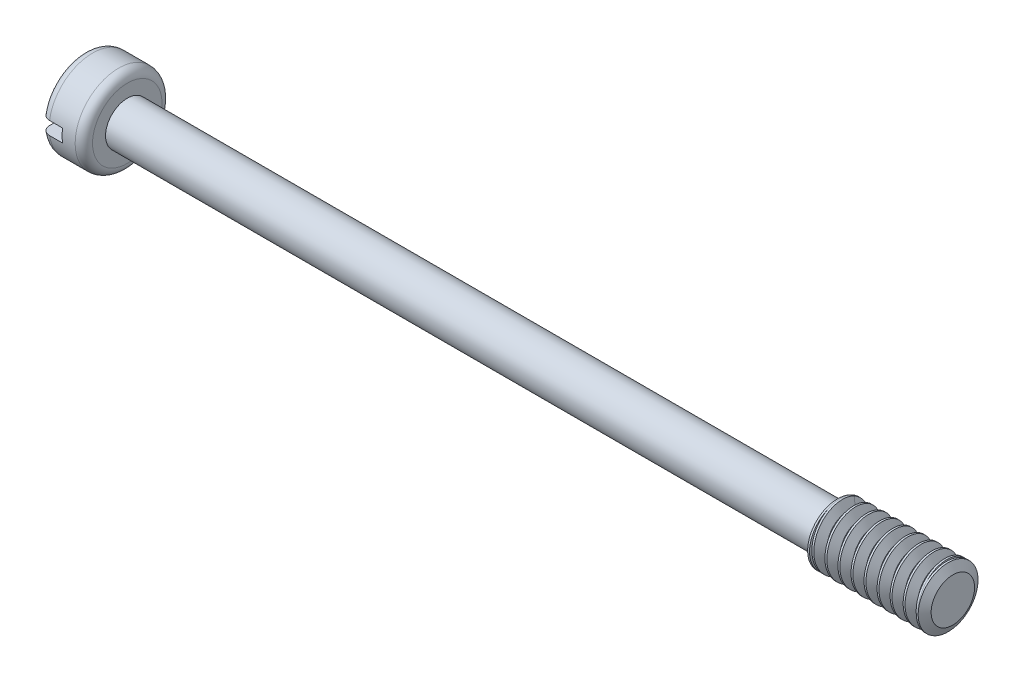
SolidWorks part; units mm, degrees
ref_plane "前视基准面" through (0, 0, 0) normal (0, 0, 1) x (1, 0, 0)
ref_plane "上视基准面" through (0, 0, 0) normal (0, 1, 0) x (1, 0, 0)
ref_plane "右视基准面" through (0, 0, 0) normal (1, 0, 0) x (0, 0, -1)
sketch "草图1" plane through (0, 0, 0) normal (0, 0, 1) x (1, 0, 0)
  line L0 (0, 0) -> (20, 0)
  line L1 (20, 0) -> (20, 0.5)
  line L2 (20, 0.5) -> (1, 0.5)
  line L3 (1, 0.5) -> (1, 0.8)
  line L4 (0.8, 1) -> (0.2, 1)
  line L5 (0, 0.8) -> (0, 0)
  arc A0 (0.2, 1) -> (0, 0.8) centre (0.2, 0.8) ccw
  arc A1 (1, 0.8) -> (0.8, 1) centre (0.8, 0.8) ccw
  point P9 (0, 1)
  point P12 (1, 1)
  dimension "D5" = 0.2
  dimension "D1" = 1
  dimension "D2" = 20
  dimension "D3" = 0.5
  dimension "D4" = 1
revolve "旋转1" add sketch "草图1" angle 360 about L0
thread "螺纹线1" pitch 0.35 method extrude profile "螺纹线轮廓1" start angle 0, offset 0, length 2.5, pitch 0.3, diameter 1
ref_plane "基准面4" through (20, 0, 0.5) normal (0, -1, 0) x (0, 0, 1)
sketch "螺纹线轮廓1" plane through (20, 0, 0.5) normal (0, -1, 0) x (0, 0, 1)
  line L0 (0, 0) -> (0, 0.35) construction
  line L1 (0, 0) -> (0.1894, 0.1094)
  line L2 (0.1894, 0.1094) -> (0.1894, 0.1531)
  line L3 (0.1894, 0.1531) -> (0, 0.2625)
  line L4 (0.1894, 0.1312) -> (0, 0.1312) construction
  line L11 (0, 0) -> (0, 0.2625)
  point P2 (0, 0)
  dimension "Pitch" = 0.35
  dimension "Profile_Angle" = 60
  dimension "Profile_Land" = 0.0437
  dimension "Profile_Height" = 0.1894
sketch "草图5" plane through (0, 0, 0) normal (0, -1, 0) x (1, 0, 0)
  line L0 (0, 0) -> (20.9351, 0) construction
  line L4 (19.8906, 0.6894) -> (19.8469, 0.6894)
  line L5 (19.8469, 0.6894) -> (19.7375, 0.5)
  line L6 (19.7375, 0.5) -> (20, 0.5)
  line L7 (20, 0.5) -> (19.8906, 0.6894)
  line L8 (19.8906, 0.6894) -> (19.8469, 0.6894)
  line L9 (19.8469, 0.6894) -> (19.7375, 0.5)
  line L10 (19.7375, 0.5) -> (20, 0.5)
  line L11 (20, 0.5) -> (19.8906, 0.6894)
  dimension "D1" = 0
revolve "旋转2" add sketch "草图5" angle 360 about L0
sketch "草图6" plane through (0, 0, 0) normal (0, -0.5, -0.866) x (-1, 0, 0)
  line L4 (-17.3469, 0.6894) -> (-17.3906, 0.6894)
  line L5 (-17.3906, 0.6894) -> (-17.5, 0.5)
  line L6 (-17.5, 0.5) -> (-17.2375, 0.5)
  line L7 (-17.2375, 0.5) -> (-17.3469, 0.6894)
  line L8 (-17.3469, 0.6894) -> (-17.3906, 0.6894)
  line L9 (-17.3906, 0.6894) -> (-17.5, 0.5)
  line L10 (-17.5, 0.5) -> (-17.2375, 0.5)
  line L11 (-17.2375, 0.5) -> (-17.3469, 0.6894)
  dimension "D1" = 0
revolve "旋转3" add sketch "草图6" angle 360 about L0
sketch "草图7" plane through (0, 0, 0) normal (-1, 0, 0) x (0, 0, 1)
  line L1 (-1, 0.15) -> (1, 0.15)
  line L2 (-1, 0.15) -> (-1, -0.15)
  line L3 (-1, -0.15) -> (1, -0.15)
  line L4 (1, 0.15) -> (1, -0.15)
  line L5 (-1, 0.15) -> (1, -0.15) construction
  line L6 (-1, -0.15) -> (1, 0.15) construction
  line L7 (0.15, -0.8) -> (-0.15, -0.8)
  line L8 (0.15, -0.8) -> (0.15, 0.8)
  line L9 (0.15, 0.8) -> (-0.15, 0.8)
  line L10 (-0.15, -0.8) -> (-0.15, 0.8)
  line L11 (0.15, -0.8) -> (-0.15, 0.8) construction
  line L12 (0.15, 0.8) -> (-0.15, -0.8) construction
  circle A0 centre (0, 0) radius 1 construction
  circle A1 centre (0, 0) radius 0.8 construction
  point P0 (0, 0)
  point P6 (0, 0)
  dimension "D1" = 0.3
  dimension "D2" = 0.3
extrude "切除-拉伸1" cut sketch "草图7" against normal blind 0.5 contours L3 L4 L1 L2 | L8 L9 L10 L7
